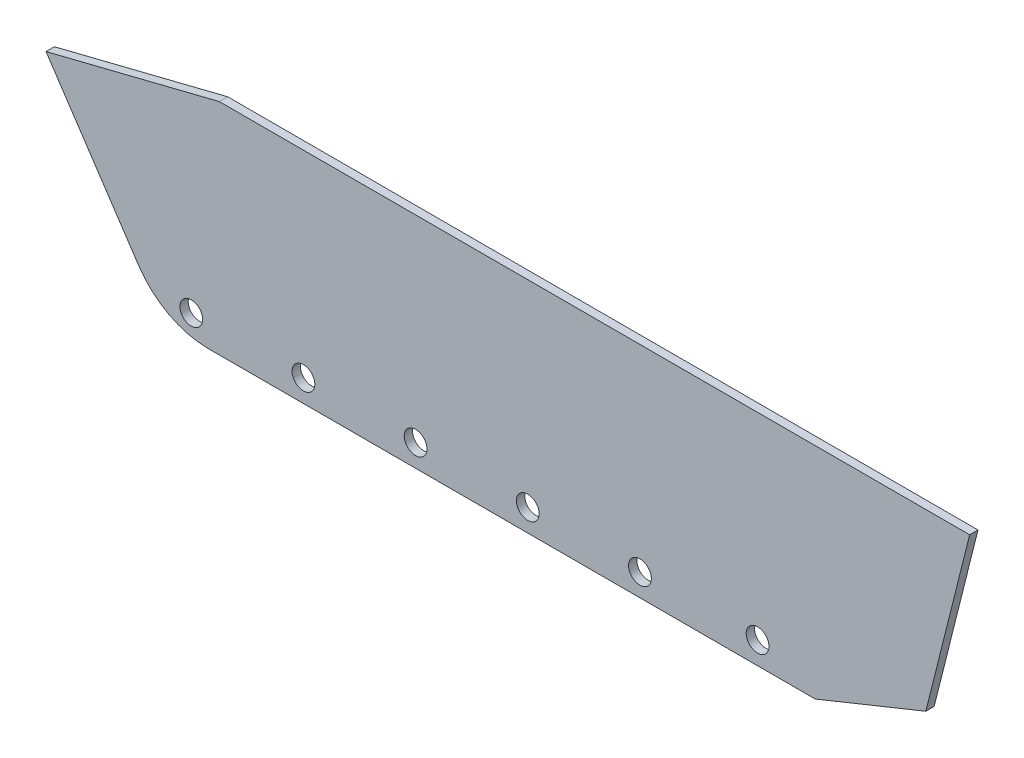
SolidWorks part; units mm, degrees
material "5052-H34"
ref_plane "Front Plane" through (0, 0, 0) normal (0, 0, 1) x (1, 0, 0)
ref_plane "Top Plane" through (0, 0, 0) normal (0, 1, 0) x (1, 0, 0)
ref_plane "Right Plane" through (0, 0, 0) normal (1, 0, 0) x (0, 0, -1)
sketch "Sketch1" plane through (0, 0, 0) normal (0, 0, 1) x (1, 0, 0)
  line L1 (428.1206, 33.3333) -> (428.1206, 28.5708)
  line L3 (428.1206, 28.5708) -> (0, 28.5708)
  line L4 (0, 28.5708) -> (-98.8794, 3.851)
  line L6 (-98.8794, 3.851) -> (-31.8794, -96.649)
  line L7 (428.1206, 28.5708) -> (403.1206, -71.149)
  line L9 (403.1206, -71.149) -> (366, -96.649)
  line L10 (-31.8794, -96.649) -> (366, -96.649)
  circle A0 centre (-16, -83.899) radius 6.5
  circle A1 centre (48, -83.899) radius 6.5
  circle A2 centre (112, -83.899) radius 6.5
  circle A3 centre (176, -83.899) radius 6.5
  circle A4 centre (240, -83.899) radius 6.5
  circle A5 centre (307.1206, -83.899) radius 6.5
  point P0 (-48.8794, -71.149)
  point P2 (-31.8794, -96.649)
  point P8 (48, -83.899)
  point P9 (403.1206, -71.149)
  dimension "D2" = 64
  dimension "D4" = 64
  dimension "D1" = 25.5
  dimension "D3" = 75
  dimension "D5" = 25
  dimension "D6" = 96
  dimension "D7" = 527
  dimension "D9" = 64
  dimension "D10" = 64
  dimension "D11" = 64
  dimension "D12" = 123.69
  dimension "D13" = 12.75
extrude "Boss-Extrude1" add sketch "Sketch1" along normal blind 4.7625 contours L3 L4 L6 L10 L9 L7
extrude "Cut-Extrude1" cut sketch "Sketch1<4>" along normal through all contours A0 | A1 | A2 | A3 | A4 | A5 region at (-16, -83.899, 0)
sketch "Sketch1<4>" plane through (0, 0, 0) normal (0, 0, 1) x (1, 0, 0) same geometry as "Sketch1"
sketch "Sketch2" plane through (0, 0, 0) normal (0, 0, -1) x (-1, 0, 0)
  circle A0 centre (-275.1206, -83.899) radius 6.5
  circle A2 centre (-233.5603, -132.5687) radius 6.5
  circle A3 centre (-192, -83.899) radius 6.5
  circle A4 centre (-128, -83.899) radius 6.5
  circle A5 centre (-64, -83.899) radius 6.5
  circle A6 centre (0, -83.899) radius 6.5
  dimension "D2" = 0
  dimension "D3" = 64
  dimension "D4" = 64
  dimension "D5" = 64
  dimension "D6" = 64
  dimension "D7" = 64
  dimension "D1" = 32
sketch "Sketch5" plane through (0, 0, 0) normal (0, 0, -1) x (-1, 0, 0)
  line L0 (48.8794, -71.149) -> (-14.2353, -96.649)
  line L1 (31.8794, -96.649) -> (-366, -96.649) construction
  line L2 (-14.2353, -96.649) -> (31.8794, -96.649)
  line L3 (31.8794, -96.649) -> (48.8794, -71.149)
  line L6 (-366, -96.649) -> (-403.1206, -71.149)
  line L7 (-403.1206, -71.149) -> (-352, -71.149)
  line L9 (-352, -71.149) -> (-326.5, -96.649)
  line L11 (-366, -96.649) -> (-326.5, -96.649)
  dimension "D1" = 22
  dimension "D2" = 45
extrude "Cut-Extrude2" [suppressed] cut sketch "Sketch5" against normal up to next
sketch "Sketch6" plane through (0, 0, 4.7625) normal (0, 0, 1) x (1, 0, 0)
  line L0 (-48.8794, -71.149) -> (14.2353, -96.649)
  line L1 (-31.8794, -96.649) -> (366, -96.649) construction
  line L2 (14.2353, -96.649) -> (-31.8794, -96.649)
  line L3 (-31.8794, -96.649) -> (-48.8794, -71.149)
  dimension "D1" = 158
fillet "Fillet1" radius 48 1 edges at (-31.8794, -96.649, 2.3813)
sketch "Sketch7" plane through (0, 0, 4.7625) normal (0, 0, 1) x (1, 0, 0)
  line L0 (403.1206, -71.149) -> (340.0059, -96.649)
  line L1 (-31.8794, -96.649) -> (366, -96.649) construction
  line L2 (340.0059, -96.649) -> (366, -96.649)
  line L3 (366, -96.649) -> (403.1206, -71.149)
  dimension "D1" = 22
extrude "Cut-Extrude3" cut sketch "Sketch7" against normal blind 10
sketch "Sketch9" plane through (0, 0, 0) normal (0, 0, -1) x (-1, 0, 0)
  line L0 (-403.1206, -71.149) -> (48.8794, -71.149)
  line L1 (48.8794, -71.149) -> (48.8794, -114.9143)
  line L2 (48.8794, -114.9143) -> (-403.1206, -114.9143)
  line L3 (-403.1206, -114.9143) -> (-403.1206, -71.149)
extrude "Cut-Extrude4" [suppressed] cut sketch "Sketch9" against normal blind 10
